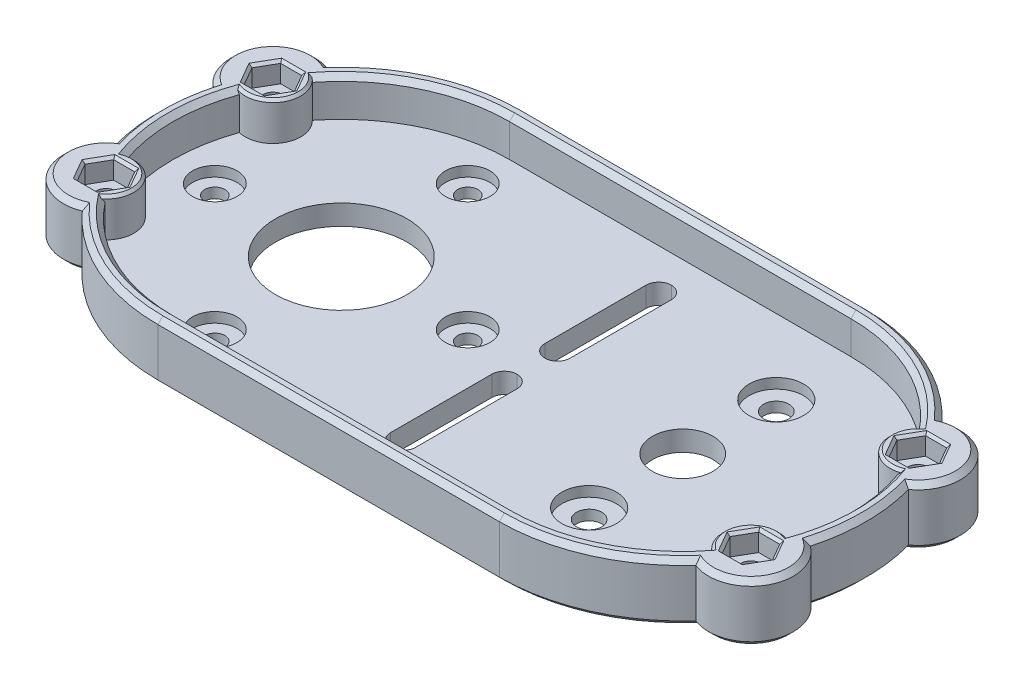
SolidWorks part; units mm, degrees
ref_plane "Front Plane" through (0, 0, 0) normal (0, 0, 1) x (1, 0, 0)
ref_plane "Top Plane" through (0, 0, 0) normal (0, 1, 0) x (1, 0, 0)
ref_plane "Right Plane" through (0, 0, 0) normal (1, 0, 0) x (0, 0, -1)
sketch "Sketch1" plane through (0, 0, 0) normal (0, 1, 0) x (1, 0, 0)
  line L0 (-54.6071, 0) -> (141.8943, 0) construction
  line L1 (67.5, 18.5) -> (67.5, -18.5) construction
  line L2 (-30, 16.5) -> (-30, -16.5) construction
  line L3 (97.5, 16.5) -> (97.5, -16.5) construction
  line L4 (0, 36.25) -> (67.5, 36.25)
  line L5 (0, -36.25) -> (67.5, -36.25)
  line L6 (0, 20.25) -> (67.5, 20.25) construction
  line L7 (0, -20.25) -> (67.5, -20.25) construction
  line L8 (35, -27.75) -> (40, -27.75)
  line L9 (35, 2.75) -> (40, 2.75)
  line L10 (35, 2.75) -> (35, 27.75)
  line L11 (35, 27.75) -> (40, 27.75)
  line L12 (40, 2.75) -> (40, 27.75)
  line L13 (35, 2.75) -> (40, 27.75) construction
  line L14 (35, 27.75) -> (40, 2.75) construction
  line L15 (40, -2.75) -> (40, -27.75)
  line L16 (35, -2.75) -> (40, -2.75)
  line L17 (35, -2.75) -> (35, -27.75)
  circle A0 centre (0, 0) radius 13
  circle A1 centre (0, 0) radius 25 construction
  circle A2 centre (0, 25) radius 2
  circle A3 centre (25, 0) radius 2
  circle A4 centre (0, -25) radius 2
  circle A5 centre (-25, 0) radius 2
  arc A6 (0, 36.25) -> (-26.8948, 24.305) centre (0, 0) ccw
  circle A7 centre (67.5, 0) radius 6
  circle A8 centre (67.5, 18.5) radius 2.5
  circle A9 centre (67.5, -18.5) radius 2.5
  circle A10 centre (-30, 16.5) radius 2
  circle A11 centre (-30, -16.5) radius 2
  circle A12 centre (97.5, -16.5) radius 2
  circle A13 centre (97.5, 16.5) radius 2
  arc A14 (-26.8948, 24.305) -> (-34.9287, 9.6979) centre (-30, 16.5) ccw
  arc A15 (-34.9287, -9.6979) -> (-26.8948, -24.305) centre (-30, -16.5) ccw
  arc A16 (102.4287, 9.6979) -> (94.3948, 24.305) centre (97.5, 16.5) ccw
  arc A17 (94.3948, -24.305) -> (102.4287, -9.6979) centre (97.5, -16.5) ccw
  arc A18 (67.5, -36.25) -> (94.3948, -24.305) centre (67.5, 0) ccw
  circle A19 centre (0, 0) radius 20.25 construction
  circle A21 centre (67.5, 0) radius 20.25 construction
  arc A22 (-34.9287, 9.6979) -> (-34.9287, -9.6979) centre (0, 0) ccw
  arc A23 (-26.8948, -24.305) -> (0, -36.25) centre (0, 0) ccw
  arc A24 (94.3948, 24.305) -> (67.5, 36.25) centre (67.5, 0) ccw
  arc A25 (102.4287, -9.6979) -> (102.4287, 9.6979) centre (67.5, 0) ccw
  point P38 (37.5, 15.25)
  dimension "D1" = 26
  dimension "D2" = 50
  dimension "D3" = 4
  dimension "D4" = 72.5
  dimension "D5" = 12
  dimension "D7" = 5
  dimension "D10" = 4
  dimension "D11" = 16.8
  dimension "D14" = 72.5
  dimension "D15" = 40.5
  dimension "D6" = 67.5
  dimension "D8" = 37
  dimension "D9" = 33
  dimension "D12" = 30
  dimension "D13" = 30
  dimension "D16" = 5
  dimension "D17" = 25
  dimension "D18" = 12.5
  dimension "D19" = 2.75
extrude "Boss-Extrude1" add sketch "Sketch1" along normal blind 4
fillet "Fillet1" radius 2.5 8 edges at (40, 2, 27.75) (35, 2, 27.75) (40, 2, 2.75) (35, 2, 2.75) (35, 2, -2.75) (40, 2, -2.75) (40, 2, -27.75) (35, 2, -27.75)
sketch "Sketch2" plane through (0, 4, 0) normal (0, 1, 0) x (1, 0, 0)
  circle A0 centre (67.5, 18.5) radius 5.4
  circle A1 centre (67.5, -18.5) radius 5.4
  circle A2 centre (0, 25) radius 4.4
  circle A3 centre (25, 0) radius 4.4
  circle A4 centre (-25, 0) radius 4.4
  circle A5 centre (0, -25) radius 4.4
  dimension "D1" = 8.8
  dimension "D2" = 10.8
extrude "Cut-Extrude1" cut sketch "Sketch2" against normal blind 2
sketch "Sketch5" plane through (0, 4, 0) normal (0, 1, 0) x (1, 0, 0)
  line L0 (0, 33.25) -> (67.5, 33.25)
  line L7 (0, -33.25) -> (67.5, -33.25)
  line L8 (0, 36.25) -> (67.5, 36.25)
  line L9 (0, -36.25) -> (67.5, -36.25)
  circle A0 centre (-30, 16.5) radius 2
  circle A1 centre (97.5, 16.5) radius 2
  circle A2 centre (97.5, -16.5) radius 2
  circle A3 centre (-30, -16.5) radius 2
  circle A4 centre (-30, 16.5) radius 2 construction
  circle A5 centre (-30, -16.5) radius 2 construction
  circle A6 centre (97.5, 16.5) radius 2 construction
  circle A7 centre (97.5, -16.5) radius 2 construction
  circle A12 centre (0, 0) radius 20.28 construction
  circle A13 centre (67.5, 0) radius 20.28 construction
  arc A14 (0, 33.25) -> (-26.1983, 20.4746) centre (0, 0) ccw
  arc A15 (93.6983, 20.4746) -> (67.5, 33.25) centre (67.5, 0) ccw
  arc A16 (67.5, -33.25) -> (93.6983, -20.4746) centre (67.5, 0) ccw
  arc A17 (0, -36.25) -> (-26.8948, -24.305) centre (0, 0) cw
  arc A18 (0, 36.25) -> (-26.8948, 24.305) centre (0, 0) ccw
  arc A19 (67.5, 36.25) -> (94.3948, 24.305) centre (67.5, 0) cw
  arc A20 (67.5, -36.25) -> (94.3948, -24.305) centre (67.5, 0) ccw
  arc A21 (-34.9287, 9.6979) -> (-34.9287, -9.6979) centre (0, 0) ccw
  arc A22 (-34.9287, 9.6979) -> (-34.9287, -9.6979) centre (0, 0) ccw construction
  arc A23 (102.4287, 9.6979) -> (102.4287, -9.6979) centre (67.5, 0) cw
  arc A24 (-31.3208, 11.161) -> (-26.1983, 20.4746) centre (-30, 16.5) ccw
  arc A26 (98.8208, -11.161) -> (93.6983, -20.4746) centre (97.5, -16.5) ccw
  arc A27 (93.6983, 20.4746) -> (98.8208, 11.161) centre (97.5, 16.5) ccw
  arc A28 (-26.1983, -20.4746) -> (-31.3208, -11.161) centre (-30, -16.5) ccw
  arc A29 (-26.8948, 24.305) -> (-34.9287, 9.6979) centre (-30, 16.5) ccw
  arc A30 (-34.9287, -9.6979) -> (-26.8948, -24.305) centre (-30, -16.5) ccw
  arc A31 (-34.9287, -9.6979) -> (-26.8948, -24.305) centre (-30, -16.5) ccw construction
  arc A32 (94.3948, 24.305) -> (102.4287, 9.6979) centre (97.5, 16.5) cw
  arc A33 (102.4287, -9.6979) -> (94.3948, -24.305) centre (97.5, -16.5) cw
  arc A34 (94.3948, -24.305) -> (102.4287, -9.6979) centre (97.5, -16.5) ccw construction
  arc A35 (-31.3208, 11.161) -> (-31.3208, -11.161) centre (0, 0) ccw
  arc A36 (98.8208, -11.161) -> (98.8208, 11.161) centre (67.5, 0) ccw
  arc A37 (-26.1983, -20.4746) -> (0, -33.25) centre (0, 0) ccw
  point P21 (94.5554, -24.1261)
  point P24 (102.4287, -9.6979)
  dimension "D1" = 40.56
  dimension "D2" = 66.5
  dimension "D4" = 66.5
  dimension "D5" = 11
  dimension "D6" = 11
  dimension "D7" = 11
  dimension "D8" = 11
extrude "Boss-Extrude2" add sketch "Sketch5" along normal blind 7.5
sketch "Sketch6" plane through (0, 11.5, 0) normal (0, 1, 0) x (1, 0, 0)
  line L1 (-25.8431, 16.5) -> (-27.9215, 20.1)
  line L2 (-27.9215, 20.1) -> (-32.0785, 20.1)
  line L3 (-32.0785, 20.1) -> (-34.1569, 16.5)
  line L4 (-34.1569, 16.5) -> (-32.0785, 12.9)
  line L5 (-32.0785, 12.9) -> (-27.9215, 12.9)
  line L6 (-27.9215, 12.9) -> (-25.8431, 16.5)
  line L7 (-34.1569, -16.5) -> (-32.0785, -20.1)
  line L8 (-32.0785, -20.1) -> (-27.9215, -20.1)
  line L9 (-27.9215, -20.1) -> (-25.8431, -16.5)
  line L10 (-25.8431, -16.5) -> (-27.9215, -12.9)
  line L11 (-27.9215, -12.9) -> (-32.0785, -12.9)
  line L12 (-32.0785, -12.9) -> (-34.1569, -16.5)
  line L13 (101.6569, 16.5) -> (99.5785, 20.1)
  line L14 (99.5785, 20.1) -> (95.4215, 20.1)
  line L15 (95.4215, 20.1) -> (93.3431, 16.5)
  line L16 (93.3431, 16.5) -> (95.4215, 12.9)
  line L17 (95.4215, 12.9) -> (99.5785, 12.9)
  line L18 (99.5785, 12.9) -> (101.6569, 16.5)
  line L19 (99.5785, -20.1) -> (101.6569, -16.5)
  line L20 (101.6569, -16.5) -> (99.5785, -12.9)
  line L21 (99.5785, -12.9) -> (95.4215, -12.9)
  line L22 (95.4215, -12.9) -> (93.3431, -16.5)
  line L23 (93.3431, -16.5) -> (95.4215, -20.1)
  line L24 (95.4215, -20.1) -> (99.5785, -20.1)
  circle A0 centre (-30, 16.5) radius 3.6 construction
  circle A1 centre (-30, -16.5) radius 3.6 construction
  circle A2 centre (97.5, 16.5) radius 3.6 construction
  circle A3 centre (97.5, -16.5) radius 3.6 construction
  dimension "D1" = 7.2
  dimension "D2" = 7.2
  dimension "D3" = 7.2
  dimension "D4" = 7.2
extrude "Cut-Extrude2" cut sketch "Sketch6" against normal blind 4
chamfer "Chamfer1" distance 1 angle 45 32 edges at (-37.3602, 0, -20.5481) (-36.25, 0, 0) (-37.3602, 0, 20.5481) (-14.7141, 0, 33.1294) (-14.7141, 0, -33.1294) (33.75, 0, 36.25) (33.75, 0, -36.25) (82.2141, 0, 33.1294) (104.8602, 0, 20.5481) (103.75, 0, 0) (104.8602, 0, -20.5481) (82.2141, 0, -33.1294) (82.0736, 11.5, 29.886) (33.75, 11.5, 33.25) (-14.5736, 11.5, 29.886) (-33.25, 11.5, 0) (-37.3602, 11.5, -20.5481) (-37.3602, 11.5, 20.5481) (-36.25, 11.5, 0) (-14.5736, 11.5, -29.886) (33.75, 11.5, -33.25) (82.0736, 11.5, -29.886) (100.75, 11.5, 0) (-14.7141, 11.5, 33.1294) (-14.7141, 11.5, -33.1294) (33.75, 11.5, 36.25) (33.75, 11.5, -36.25) (82.2141, 11.5, 33.1294) (104.8602, 11.5, 20.5481) (103.75, 11.5, 0) (104.8602, 11.5, -20.5481) (82.2141, 11.5, -33.1294)
chamfer "Chamfer2" distance 0.5 angle 45 28 edges at (-30, 11.5, -12.9) (-33.1177, 11.5, -14.7) (-33.1177, 11.5, -18.3) (-30, 11.5, -20.1) (-26.8823, 11.5, -14.7) (-26.8823, 11.5, -18.3) (-25.1808, 11.5, -13.8494) (-30, 11.5, 20.1) (-33.1177, 11.5, 18.3) (-33.1177, 11.5, 14.7) (-30, 11.5, 12.9) (-26.8823, 11.5, 18.3) (-26.8823, 11.5, 14.7) (-25.1808, 11.5, 13.8494) (100.6177, 11.5, 18.3) (97.5, 11.5, 20.1) (94.3823, 11.5, 18.3) (94.3823, 11.5, 14.7) (97.5, 11.5, 12.9) (100.6177, 11.5, 14.7) (92.6808, 11.5, 13.8494) (92.6808, 11.5, -13.8494) (97.5, 11.5, -12.9) (94.3823, 11.5, -14.7) (94.3823, 11.5, -18.3) (97.5, 11.5, -20.1) (100.6177, 11.5, -14.7) (100.6177, 11.5, -18.3)
